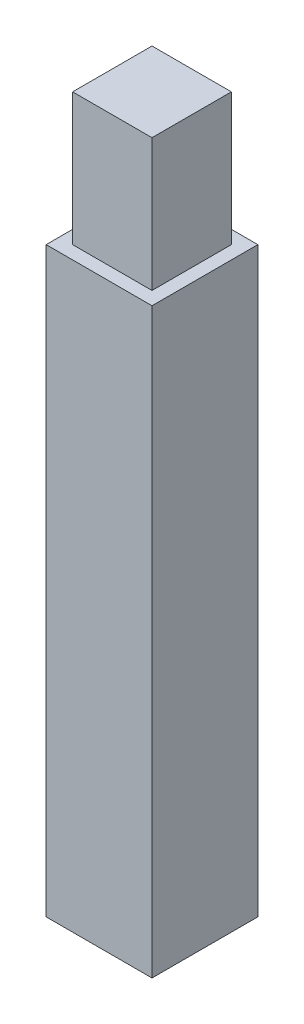
SolidWorks part; units mm, degrees
ref_plane "Front Plane" through (0, 0, 0) normal (0, 0, 1) x (1, 0, 0)
ref_plane "Top Plane" through (0, 0, 0) normal (0, 1, 0) x (1, 0, 0)
ref_plane "Right Plane" through (0, 0, 0) normal (1, 0, 0) x (0, 0, -1)
sketch "Sketch1" plane through (0, 0, 0) normal (0, 1, 0) x (1, 0, 0)
  line L1 (0, 0) -> (4, 0)
  line L2 (0, 0) -> (0, 4)
  line L3 (0, 4) -> (4, 4)
  line L4 (4, 0) -> (4, 4)
  dimension "D1" = 4
  dimension "D2" = 4
extrude "Boss-Extrude1" add sketch "Sketch1" along normal blind 22
sketch "Sketch2" plane through (0, 22, 0) normal (0, 1, 0) x (1, 0, 0)
  line L0 (4, 4) -> (0, 4) construction
  line L1 (0.5, 0.5) -> (3.5, 0.5)
  line L2 (0.5, 0.5) -> (0.5, 3.5)
  line L3 (0.5, 3.5) -> (3.5, 3.5)
  line L4 (3.5, 0.5) -> (3.5, 3.5)
  line L5 (0, 4) -> (0, 0) construction
  dimension "D1" = 3
  dimension "D2" = 3
  dimension "D3" = 0.5
  dimension "D4" = 0.5
extrude "Boss-Extrude2" add sketch "Sketch2" along normal blind 5
